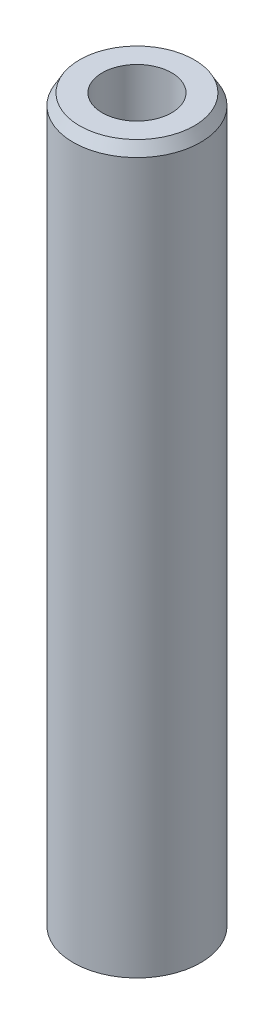
SolidWorks part; units mm, degrees
ref_plane "Front Plane" through (0, 0, 0) normal (0, 0, 1) x (1, 0, 0)
ref_plane "Top Plane" through (0, 0, 0) normal (0, 1, 0) x (1, 0, 0)
ref_plane "Right Plane" through (0, 0, 0) normal (1, 0, 0) x (0, 0, -1)
sketch "Sketch1" plane through (0, 0, 0) normal (0, 1, 0) x (1, 0, 0)
  circle A0 centre (0, 0) radius 10
  dimension "SHAFT_OD" = 20
extrude "Boss-Extrude1" add sketch "Sketch1" along normal blind 114.2828
sketch "Sketch2" plane through (0, 0, 0) normal (0, 1, 0) x (1, 0, 0)
  circle A0 centre (0, 0) radius 5.4499
  dimension "BORE_D" = 10.8999
extrude "Cut-Extrude1" cut sketch "Sketch2" along normal through all
chamfer "Chamfer1" distance 1.7424 angle 30 2 edges at (0, 114.2828, 10) (0, 0, 10) first distance on face at (0, 114.2828, 10) first distance on face at (0, 0, 5.4499)
